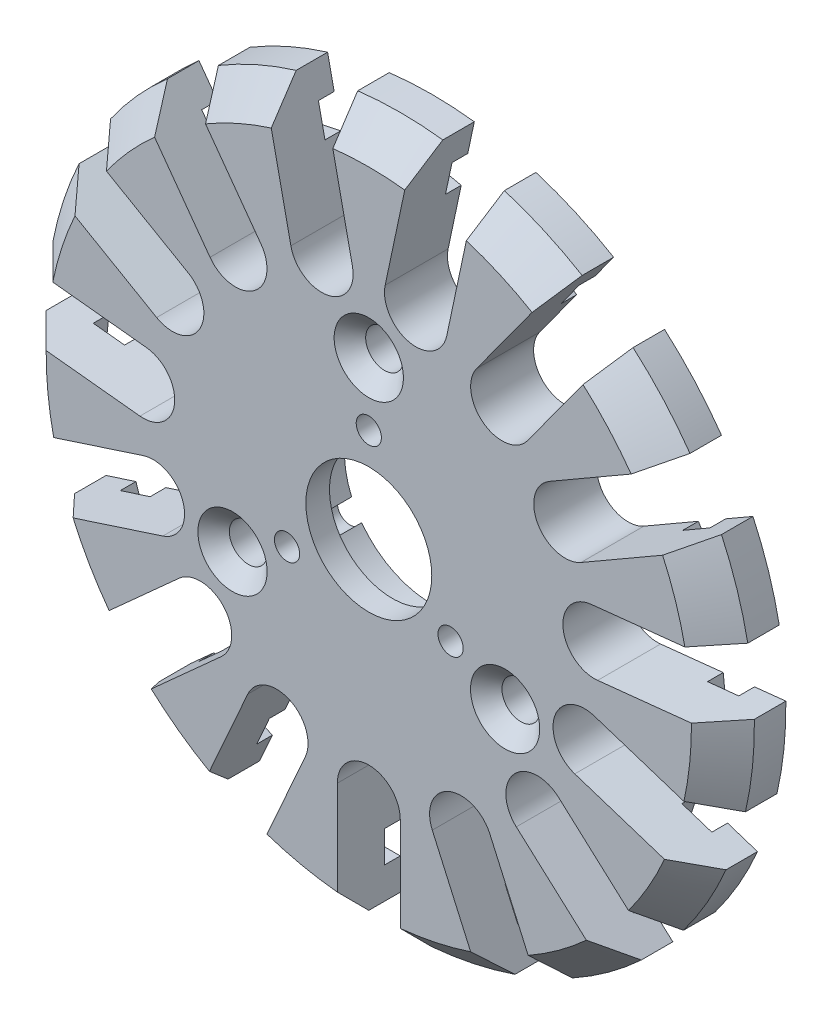
SolidWorks part; units mm, degrees
material "Liga 1060"
ref_plane "Plano frontal" through (0, 0, 0) normal (0, 0, 1) x (1, 0, 0)
ref_plane "Plano superior" through (0, 0, 0) normal (0, 1, 0) x (1, 0, 0)
ref_plane "Plano direito" through (0, 0, 0) normal (1, 0, 0) x (0, 0, -1)
sketch "Esboço1" plane through (0, 0, 0) normal (0, 0, 1) x (1, 0, 0)
  circle A0 centre (0, 0) radius 22.5
  dimension "D1" = 45
extrude "Ressalto-extrusão1" add sketch "Esboço1" along normal blind 4
chamfer "Chanfro1" distance 2 angle 45 1 edges at (22.5, 0, 4)
sketch "Esboço4" plane through (0, 0, 0) normal (0, 0, -1) x (-1, 0, 0)
  circle A0 centre (0, 0) radius 5.55
  dimension "D1" = 11.1
extrude "Corte-extrusão2" cut sketch "Esboço4" against normal blind 2.5 contours A0
sketch "Esboço5" plane through (0, 0, 2.5) normal (0, 0, -1) x (-1, 0, 0)
  circle A0 centre (0, 0) radius 4
  dimension "D1" = 8
extrude "Corte-extrusão3" cut sketch "Esboço5" against normal blind 2
sketch "Esboço6" plane through (0, 0, 0) normal (0, 0, -1) x (-1, 0, 0)
  line L0 (0, 0) -> (0, -22.5) construction
  line L1 (2, -22.4109) -> (2, -14.4109)
  line L2 (-2, -14.4109) -> (-2, -22.4109)
  circle A0 centre (0, 0) radius 22.5 construction
  arc A1 (-2, -22.4109) -> (2, -22.4109) centre (0, 0) ccw
  arc A2 (2, -14.4109) -> (-2, -14.4109) centre (0, -14.4109) ccw
  dimension "D1" = 4
  dimension "D2" = 8
extrude "Corte-extrusão4" cut sketch "Esboço6" against normal blind 4
pattern_circular "PadrãoCircular1" count 15 over 360 about axis through (0, 0, 2.5) along (0, 0, -1) of "Corte-extrusão4"
sketch "Esboço8" plane through (0, 0, 0) normal (0, 0, -1) x (-1, 0, 0)
  circle A0 centre (0, 0) radius 20.5
  circle A1 centre (0, 0) radius 18.5
  dimension "D1" = 41
  dimension "D2" = 37
sketch "Esboço9" plane through (0, 0, 4) normal (0, 0, 1) x (1, 0, 0)
  circle A0 centre (0, 0) radius 6
  circle A1 centre (0, 0) radius 4
  circle A2 centre (0, 0) radius 10
  point P4 (0, 6)
  point P6 (0, 10)
  dimension "D1" = 8
  dimension "D2" = 12
  dimension "D3" = 20
hole_wizard "Broca de rosquear para tarraxa de M21" positions "3DSketch1" profile "Esboço10" hole size "M2" standard "ISO" end condition through all
sketch3d "3DSketch1"
  point P0 (0, 6, 4)
sketch "Esboço10" plane through (0, 6, 4) normal (1, 0, 0) x (0, -1, 0)
  line L0 (0, 0) -> (0, 4)
  line L1 (0, 4) -> (0.8, 4)
  line L2 (0.8, 4) -> (0.8, 0)
  line L5 (0.8, 0) -> (0, 0)
  line L11 (0, -6.35) -> (0, 107.95) construction
  dimension "Thru Hole Dia." = 1.6
  dimension "Thru Hole Depth" = 4
hole_wizard "Escareado para parafuso com cabeça escareada chata de M21" positions "3DSketch2" profile "Esboço14" countersink size "M2" standard "ISO" end condition through all
sketch3d "3DSketch2"
  point P0 (0, 10, 4)
sketch "Esboço14" plane through (0, 10, 4) normal (1, 0, 0) x (0, -1, 0)
  line L0 (0, 0) -> (0, 4)
  line L1 (0, 4) -> (1.2, 4)
  line L2 (1.2, 4) -> (1.2, 1)
  line L3 (1.2, 1) -> (2.2, 0)
  line L5 (2.2, 0) -> (0, 0)
  line L6 (-1.2, 1) -> (-2.2, 0) construction
  line L11 (0, -6.35) -> (0, 107.95) construction
  dimension "Thru Hole Dia." = 2.4
  dimension "Thru Hole Depth" = 4
  dimension "Near C'Sink Dia." = 4.4
  dimension "Near C'Sink Angle" = 90
pattern_circular "PadrãoCircular2" count 3 over 360 about axis through (0, 0, 2.5) along (0, 0, -1) of "Broca de rosquear para tarraxa de M21" reverse direction yes
sketch "Esboço12" plane through (0, 0, 0) normal (0, 0, -1) x (-1, 0, 0)
  line L2 (3.5, -20.4109) -> (-3.5, -20.4109)
  line L3 (-3.5, -20.4109) -> (-3.5, -18.4109)
  line L4 (-3.5, -18.4109) -> (3.5, -18.4109)
  line L5 (3.5, -18.4109) -> (3.5, -20.4109)
  line L6 (0, 0) -> (0, -22.5) construction
  arc A0 (-7.2883, -21.2869) -> (-2, -22.4109) centre (0, 0) ccw construction
  point P0 (0, -18.4109)
  dimension "D1" = 2
  dimension "D2" = 7
  dimension "D3" = 2
extrude "Corte-extrusão5" cut sketch "Esboço12" against normal blind 1
pattern_circular "PadrãoCircular3" count 15 over 360 about axis through (0, 0, 0) along (0, 0, -1) of "Corte-extrusão5"
pattern_circular "PadrãoCircular4" count 3 over 360 about axis through (0, 0, 4) along (0, 0, 1) of "Escareado para parafuso com cabeça escareada chata de M21"
